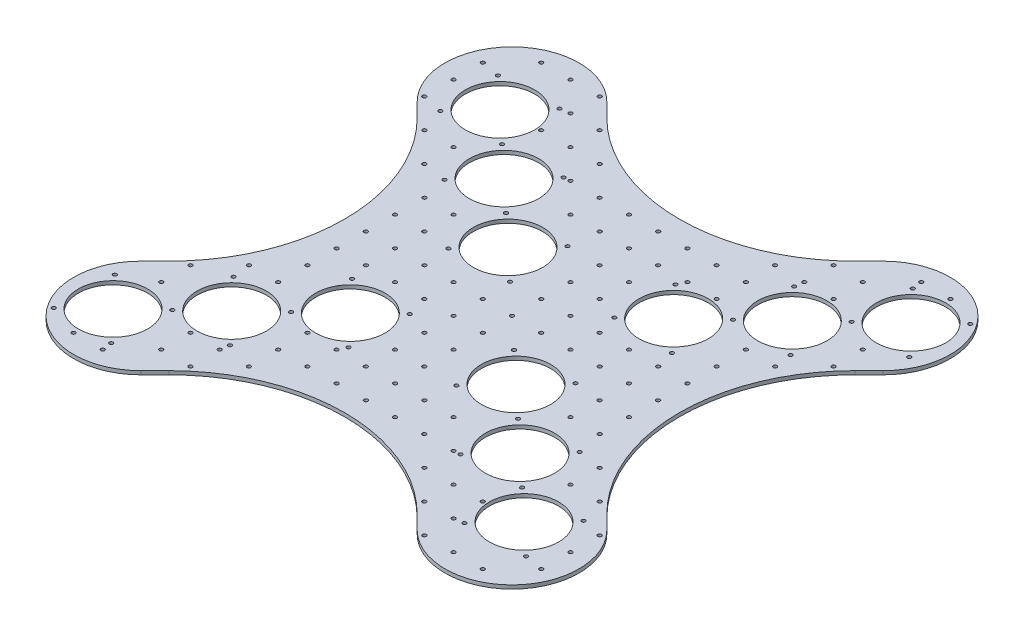
SolidWorks part; units mm, degrees
ref_plane "Front Plane" through (0, 0, 0) normal (0, 0, 1) x (1, 0, 0)
ref_plane "Top Plane" through (0, 0, 0) normal (0, 1, 0) x (1, 0, 0)
ref_plane "Right Plane" through (0, 0, 0) normal (1, 0, 0) x (0, 0, -1)
sketch "Sketch1" plane through (0, 0, 0) normal (0, 1, 0) x (1, 0, 0)
  line L5 (-190.1545, 107.7627) -> (-202.4527, 120.061)
  line L8 (-190.1545, -107.7627) -> (-202.4527, -120.061)
  line L9 (-107.7627, -190.1533) -> (-120.0616, -202.4521)
  line L10 (107.7627, -190.1533) -> (120.0616, -202.4521)
  line L11 (190.1522, -107.7627) -> (202.4515, -120.0621)
  line L12 (190.1522, 107.7627) -> (202.4515, 120.0621)
  line L13 (-161.257, -161.2564) -> (161.257, 161.2564) construction
  line L14 (-161.2564, 161.257) -> (161.2564, -161.257) construction
  line L15 (-120.0601, 202.453) -> (-107.7614, 190.1541)
  line L16 (-190.1545, 107.7627) -> (-107.7614, 190.1541) construction
  line L17 (120.063, 202.4513) -> (107.764, 190.1526)
  line L18 (-120.0601, 202.453) -> (-202.4527, 120.061) construction
  arc A1 (190.1522, 107.7627) -> (190.1522, -107.7627) centre (297.9157, 0) ccw
  arc A2 (-190.1545, 107.7627) -> (-190.1545, -107.7627) centre (-297.9179, 0) cw
  arc A3 (-107.7627, -190.1533) -> (107.7627, -190.1533) centre (0, -297.9168) cw
  arc A4 (-120.0601, 202.453) -> (-202.4527, 120.061) centre (-161.2564, 161.257) ccw
  arc A5 (120.063, 202.4513) -> (202.4515, 120.0621) centre (161.257, 161.2564) cw
  arc A6 (202.4515, -120.0621) -> (120.0616, -202.4521) centre (161.2564, -161.257) cw
  arc A7 (-120.0616, -202.4521) -> (-202.4527, -120.061) centre (-161.257, -161.2564) cw
  arc A8 (-107.7614, 190.1541) -> (107.764, 190.1526) centre (0.0021, 297.9168) ccw
  point P5 (0, 0)
  dimension "D1" = 152.4
  dimension "D2" = 1828.8
sketch "Sketch2" plane through (0, 0, 0) normal (0, 1, 0) x (1, 0, 0)
  circle A0 centre (-103.0349, 123.7443) radius 25.4
  dimension "D1" = 50.8
sketch "Sketch3" plane through (0, 0, 0) normal (0, 1, 0) x (1, 0, 0)
  line L1 (-161.2564, 161.257) -> (161.2564, -161.257) construction
  line L3 (-161.257, -161.2564) -> (161.257, 161.2564) construction
  line L4 (-164.1921, 164.1927) -> (0.0006, 328.3853) construction
  line L5 (0.0006, 328.3853) -> (164.1932, 164.1927) construction
sketch "Sketch4" plane through (0, 0, 0) normal (0, 1, 0) x (1, 0, 0)
  circle A0 centre (-160.2695, 149.8171) radius 30.1308
  circle A1 centre (178.5688, 168.1152) radius 30.1308
  dimension "D1" = 60.2615
extrude "Boss-Extrude1" add sketch "Sketch1" along normal mid plane 3.175
extrude "Cut-Extrude1" cut sketch "Sketch4" against normal mid plane 43.175
sketch "Sketch5" plane through (0, 0, 0) normal (0, 0, 1) x (1, 0, 0)
  line L0 (0, 0) -> (0, 191.7053) construction
sketch "Sketch6" plane through (0, 0, 0) normal (0, 1, 0) x (1, 0, 0)
  line L0 (-160.2695, 149.8171) -> (0, 0) construction
  line L1 (0, 0) -> (178.5688, 168.1152) construction
  circle A0 centre (125.4597, 118.1152) radius 30.1307
  circle A1 centre (178.5688, 168.1152) radius 30.1308 construction
  circle A2 centre (-106.7811, 99.8171) radius 30.1307
  circle A3 centre (-53.2927, 49.8171) radius 30.1308
  circle A4 centre (72.3507, 68.1152) radius 30.1308
  dimension "D1" = 50
  dimension "D2" = 50
  dimension "D3" = 50
  dimension "D4" = 50
extrude "Cut-Extrude2" cut sketch "Sketch6" against normal mid plane 43.175
pattern_circular "CirPattern1" count 2 over 360 about axis through (0, 0, 0) along (0, 1, 0) of "Cut-Extrude1", "Cut-Extrude2" reverse direction yes
sketch "Sketch7" plane through (0, 1.5875, 0) normal (0, 1, 0) x (1, 0, 0)
  line L0 (-161.2564, 161.257) -> (161.2564, -161.257) construction
  line L1 (0, 0) -> (113.8099, 0) construction
  line L2 (0, 0) -> (0, 66.1161) construction
  circle A0 centre (0, 0) radius 1.625
  dimension "D1" = 3.25
extrude "Cut-Extrude3" cut sketch "Sketch7" against normal through all
pattern_linear "LPattern1" count 9 spacing 25.4 along (1, 0, 0) count 9 spacing 25.4 along (0, 0, -1) skipping (0, 6), (0, 7), (0, 8), (1, 6), (1, 7), (1, 8), (2, 2), (2, 3), (2, 6), (2, 7), (2, 8), (3, 2), (3, 3), (3, 7), (3, 8), (4, 2), (4, 3), (4, 4), (4, 5), (4, 8), (5, 4), (5, 5), (5, 8), (6, 0), (6, 1), (6, 2), (6, 4), (6, 5), (6, 6), (6, 7), (7, 0), (7, 1), (7, 2), (7, 3), (7, 6), (7, 7), (8, 0), (8, 1), (8, 2), (8, 4), (8, 5), (8, 6), (8, 7), (8, 8) of "Cut-Extrude3"
pattern_linear "LPattern2" count 9 spacing 25.4 along (-1, 0, 0) count 9 spacing 25.4 along (0, 0, -1) skipping (0, 6), (0, 7), (0, 8), (1, 1), (1, 2), (1, 3), (1, 6), (1, 7), (1, 8), (2, 1), (2, 2), (2, 3), (2, 6), (2, 7), (2, 8), (3, 1), (3, 2), (3, 3), (3, 4), (3, 7), (3, 8), (4, 3), (4, 4), (4, 5), (4, 8), (5, 3), (5, 4), (5, 5), (6, 0), (6, 1), (6, 2), (6, 5), (6, 6), (6, 7), (7, 0), (7, 1), (7, 2), (7, 3), (7, 5), (7, 6), (7, 7), (8, 0), (8, 1), (8, 2), (8, 3), (8, 4), (8, 8) of "Cut-Extrude3"
sketch "Sketch8" plane through (0, 0, 0) normal (0, 1, 0) x (1, 0, 0)
  line L0 (45.7962, 43.1152) -> (205.1233, 193.1152) construction
  line L1 (-26.5485, 24.8171) -> (-187.0137, 174.8171) construction
  line L2 (-78.2927, 23.0729) -> (-28.2927, 76.5613) construction
  line L3 (-185.2695, 123.0729) -> (-135.2695, 176.5613) construction
  line L4 (-81.7811, 126.5613) -> (-131.7811, 73.0729) construction
  line L5 (47.3507, 94.6697) -> (97.3507, 41.5607) construction
  line L6 (150.4597, 91.5607) -> (100.4597, 144.6697) construction
  line L7 (203.5688, 141.5607) -> (153.5688, 194.6697) construction
  circle A0 centre (72.3507, 68.1152) radius 36.4711 construction
  circle A1 centre (125.4597, 118.1152) radius 36.4711 construction
  circle A2 centre (178.5688, 168.1152) radius 36.4711 construction
  circle A3 centre (-160.2695, 149.8171) radius 36.6095 construction
  circle A4 centre (-106.7811, 99.8171) radius 36.6095 construction
  circle A5 centre (-53.2927, 49.8171) radius 36.6095 construction
  circle A11 centre (-80.0369, 74.8171) radius 1.625
  circle A12 centre (-133.5253, 124.8171) radius 1.625
  circle A13 centre (98.9052, 93.1152) radius 1.625
  circle A14 centre (152.0143, 143.1152) radius 1.625
  circle A15 centre (-187.0137, 174.8171) radius 1.625
  circle A16 centre (-185.2695, 123.0729) radius 1.625
  circle A17 centre (-135.2695, 176.5613) radius 1.625
  circle A18 centre (-81.7811, 126.5613) radius 1.625
  circle A19 centre (-131.7811, 73.0729) radius 1.625
  circle A20 centre (-26.5485, 24.8171) radius 1.625
  circle A21 centre (-78.2927, 23.0729) radius 1.625
  circle A22 centre (-28.2927, 76.5613) radius 1.625
  circle A23 centre (45.7962, 43.1152) radius 1.625
  circle A24 centre (97.3507, 41.5607) radius 1.625
  circle A25 centre (47.3507, 94.6697) radius 1.625
  circle A26 centre (150.4597, 91.5607) radius 1.625
  circle A27 centre (100.4597, 144.6697) radius 1.625
  circle A28 centre (203.5688, 141.5607) radius 1.625
  circle A29 centre (153.5688, 194.6697) radius 1.625
  circle A30 centre (205.1233, 193.1152) radius 1.625
  point P58 (-160.2695, 149.8171)
  point P59 (-106.7811, 99.8171)
  dimension "D1" = 3.25
extrude "Cut-Extrude4" cut sketch "Sketch8" against normal mid plane 43.175
pattern_circular "CirPattern2" count 2 over 360 about axis through (0, 0, 0) along (0, 1, 0) of "LPattern2", "LPattern1", "Cut-Extrude4" reverse direction yes
